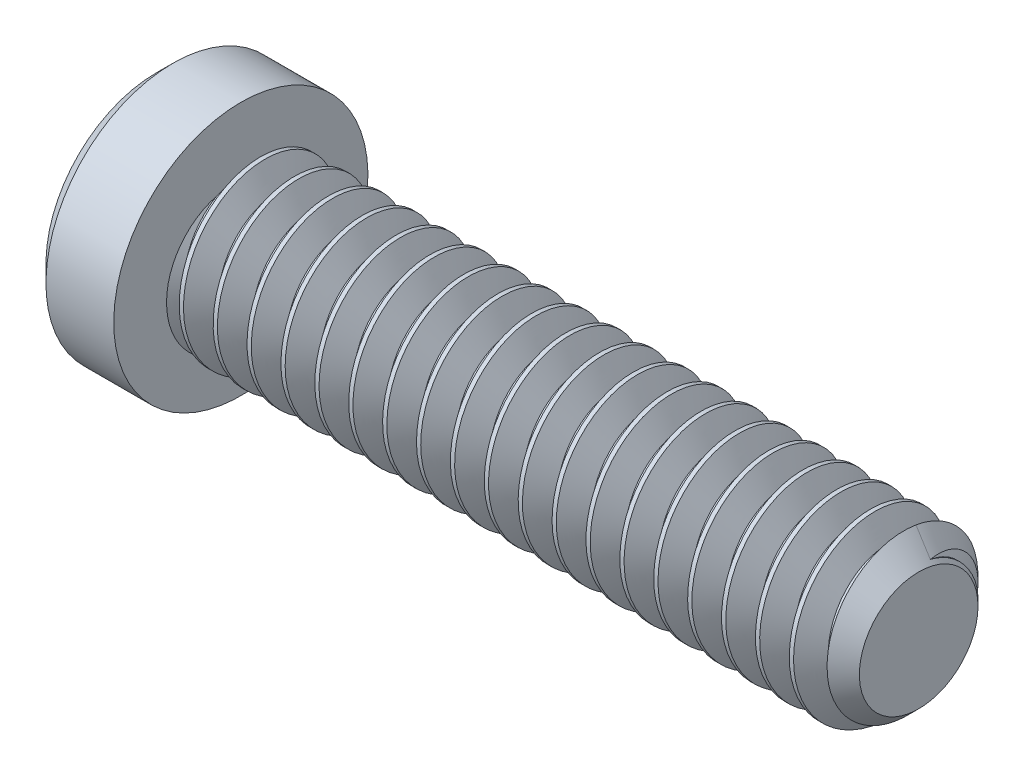
SolidWorks part; units mm, degrees
ref_plane "Front Plane" through (0, 0, 0) normal (0, 0, 1) x (1, 0, 0)
ref_plane "Top Plane" through (0, 0, 0) normal (0, 1, 0) x (1, 0, 0)
ref_plane "Right Plane" through (0, 0, 0) normal (1, 0, 0) x (0, 0, -1)
sketch "Sketch1" plane through (0, 0, 0) normal (0, 0, 1) x (1, 0, 0)
  line L0 (12.7, 0) -> (-12.7, 0) construction
  line L1 (12.7, 3.175) -> (12.7, -3.175) construction
  line L2 (-12.7, 4.7625) -> (-12.7, -4.7625) construction
  line L3 (-12.7, 4.7625) -> (-15.24, 4.7625) construction
  line L4 (-15.24, 4.7625) -> (-15.875, 4.1275) construction
  line L5 (-15.875, 4.1275) -> (-15.875, -4.1275) construction
  line L6 (-15.875, -4.1275) -> (-15.24, -4.7625) construction
  line L7 (-15.24, -4.7625) -> (-12.7, -4.7625) construction
  point P7 (-13.4874, 0)
  point P12 (7.62, -3.175)
  dimension "D1" = 45
  dimension "Dec." = 6.35
  dimension "Length" = 25.4
  dimension "Head Dia" = 9.525
  dimension "Head Height" = 3.175
  dimension "Hex Depth" = 2.3876
  dimension "Chamfer" = 0.635
  dimension "D2" = 5.08
ref_plane "Plane1" through (12.7, 0, 0) normal (1, 0, 0) x (0, 0, -1)
ref_plane "Plane2" through (-15.875, 0, 0) normal (1, 0, 0) x (0, 0, -1)
sketch "Sketch2" plane through (12.7, 0, 0) normal (1, 0, 0) x (0, 0, -1)
  circle A0 centre (0, 0) radius 3.175
extrude "Boss-Extrude1" add sketch "Sketch2" against normal up to vertex (25.4 mm away) up to point (-12.7, 0, 0)
sketch "Sketch3" plane through (12.7, 0, 0) normal (1, 0, 0) x (0, 0, -1)
  circle A0 centre (0, 0) radius 3.175 construction
  circle A1 centre (0, 0) radius 3.175
curve "Helix/Spiral1" pitch 1.27 height 26.67 radius 3.175 centre (12.7, 0, 0) axis (-1, 0, 0) start towards (0, 1, 0) parameters "Pitch"=1.27
chamfer "Chamfer1" distance 0.9525 angle 45 1 edges at (12.7, 0, -3.175)
sketch "Sketch5" plane through (0, 0, 0) normal (0, 0, 1) x (1, 0, 0)
  line L0 (12.1444, 3.175) -> (13.2556, 3.175)
  line L1 (13.2556, 3.175) -> (12.7794, 2.3501)
  line L2 (12.7794, 2.3501) -> (12.6206, 2.3501)
  line L3 (12.6206, 2.3501) -> (12.1444, 3.175)
  line L4 (12.7, 2.3501) -> (12.7, 3.175) construction
  line L5 (12.3825, 2.7626) -> (13.0175, 2.7626) construction
  dimension "D1" = 60
  dimension "D2" = 0.635
  dimension "D3" = 0.1588
sweep "Cut-Sweep1" cut profiles "Sketch5" path "Helix/Spiral1" align with end faces yes
sketch "Sketch4" plane through (-15.875, 0, 0) normal (1, 0, 0) x (0, 0, -1)
  line L0 (-4.7625, 0.7937) -> (4.7625, 0.7937) construction
  line L1 (0, 1.8331) -> (-1.5875, 0.9165)
  line L2 (-1.5875, 0.9165) -> (-1.5875, -0.9165)
  line L3 (-1.5875, -0.9165) -> (0, -1.8331)
  line L4 (0, -1.8331) -> (1.5875, -0.9165)
  line L5 (1.5875, -0.9165) -> (1.5875, 0.9165)
  line L6 (1.5875, 0.9165) -> (0, 1.8331)
  line L7 (0, 0) -> (0, 0.7937) construction
  circle A0 centre (0, 0) radius 1.5875 construction
  dimension "Hex Size" = 3.175
  dimension "D1" = 9.525
  dimension "D2" = 0.7937
sketch "Sketch6" plane through (0, 0, 0) normal (0, 0, 1) x (1, 0, 0)
  line L0 (-15.24, 4.7625) -> (-15.875, 4.1275) construction
  line L1 (-12.7, 4.7625) -> (-15.24, 4.7625) construction
  line L2 (-12.7, 4.7625) -> (-12.7, -4.7625) construction
  line L3 (-15.875, 4.1275) -> (-15.875, -4.1275) construction
  line L4 (-15.24, 4.7625) -> (-15.875, 4.1275)
  line L5 (-12.7, 4.7625) -> (-15.24, 4.7625)
  line L6 (-12.7, 4.7625) -> (-12.7, 0)
  line L7 (-15.875, 4.1275) -> (-15.875, 0)
  line L8 (-12.7, 0) -> (-15.875, 0) construction
  line L9 (-12.7, 0) -> (-15.875, 0)
revolve "Revolve1" add sketch "Sketch6" angle 360 about L8
extrude "Cut-Extrude1" cut sketch "Sketch4" along normal up to vertex (2.3876 mm away) up to point (-13.4874, 0, 0)
sketch "Sketch8" plane through (-15.875, 0, 0) normal (-1, 0, 0) x (0, 0, 1)
  circle A1 centre (0, 0) radius 1.8331
extrude "Cut-Extrude2" cut sketch "Sketch8" against normal through all draft 45
equation "\"D3@Helix/Spiral1\" = \"Length@Sketch1\"+\"Pitch@Helix/Spiral1\""
equation "\"D3@Sketch5\" = \"Pitch@Helix/Spiral1\"*.125"
equation "\"D2@Sketch5\" = \"Pitch@Helix/Spiral1\"*.50"
equation "\"D1@Chamfer1\" = \"Pitch@Helix/Spiral1\"*.75"
equation "\"D2@Sketch1\" = \"Pitch@Helix/Spiral1\"*4"
equation "\"D1@Sketch4\" = \"Head Dia@Sketch1\""
